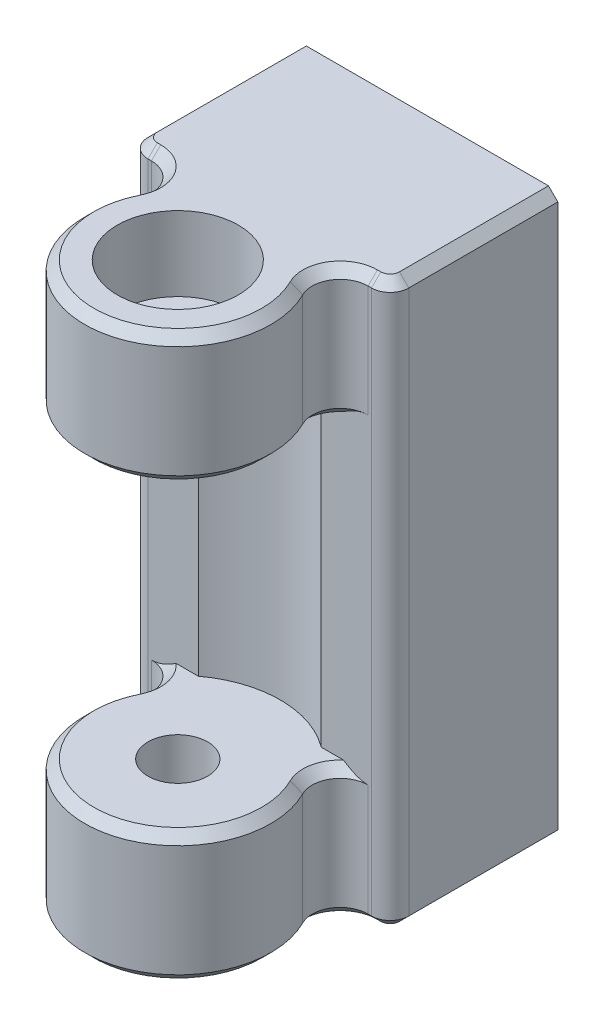
SolidWorks part; units mm, degrees
material "ABS"
ref_plane "Alzado" through (0, 0, 0) normal (0, 0, 1) x (1, 0, 0)
ref_plane "Planta" through (0, 0, 0) normal (0, 1, 0) x (1, 0, 0)
ref_plane "Vista lateral" through (0, 0, 0) normal (1, 0, 0) x (0, 0, -1)
sketch "Croquis2" plane through (0, 0, 0) normal (0, 1, 0) x (0, 0, -1)
  line L0 (0, -7) -> (0, 7)
  line L1 (0, 0) -> (-27.4728, 0) construction
  line L2 (0, 7) -> (-9, 7)
  line L3 (-9, 7) -> (-9, 5.8172)
  line L4 (-9, -7) -> (-9, -5.8172)
  line L5 (0, -7) -> (-9, -7)
  arc A2 (-11.1692, 4.4748) -> (-11.1692, -4.4748) centre (-13.4, 0) ccw
  arc A3 (-9, 5.8172) -> (-11.1692, 4.4748) centre (-10.5, 5.8172) cw
  circle A4 centre (-13.4, 0) radius 1.6
  arc A5 (-9, -5.8172) -> (-11.1692, -4.4748) centre (-10.5, -5.8172) ccw
  dimension "D1" = 14
  dimension "D2" = 9
  dimension "D3" = 10
  dimension "D5" = 1.5
  dimension "D6" = 3.2
  dimension "D4" = 13.4
extrude "Saliente-Extruir1" add sketch "Croquis2" along normal mid plane 30.2
sketch "Croquis6" plane through (0, 0, 0) normal (0, 1, 0) x (1, 0, 0)
  line L0 (-7, -9) -> (-3.3, -9)
  line L1 (3.3, -9) -> (7, -9)
  line L2 (-7, -9) -> (-7, -18.9)
  line L3 (-7, -18.9) -> (7, -18.9)
  line L4 (7, -18.9) -> (7, -9)
  arc A0 (3.3, -9) -> (-3.3, -9) centre (0, -13.4) ccw
  dimension "D1" = 11
extrude "Cortar-Extruir4" cut sketch "Croquis6" against normal mid plane 16.2
sketch "Croquis4" plane through (0, 15.1, 0) normal (0, 1, 0) x (1, 0, 0)
  circle A0 centre (0, -13.4) radius 3.25
  dimension "D1" = 6.5
extrude "Cortar-Extruir2" cut sketch "Croquis4" against normal blind 4 and the other way through all
sketch "Croquis5" plane through (0, -15.1, 0) normal (0, -1, 0) x (1, 0, 0)
  line L0 (7, 0) -> (-7, 0) construction
  line L1 (1.5011, 10.8) -> (3.0022, 13.4)
  line L2 (3.0022, 13.4) -> (1.5011, 16)
  line L3 (1.5011, 16) -> (-1.5011, 16)
  line L4 (-1.5011, 16) -> (-3.0022, 13.4)
  line L5 (-3.0022, 13.4) -> (-1.5011, 10.8)
  line L6 (-1.5011, 10.8) -> (1.5011, 10.8)
  circle A0 centre (0, 13.4) radius 2.6 construction
  dimension "D1" = 5.2
extrude "Cortar-Extruir3" cut sketch "Croquis5" against normal blind 4
fillet "Redondeo2" radius 1 2 edges at (-7, 0, 9) (7, 0, 9)
chamfer "Chaflán1" distance 0.5 angle 45 24 edges at (-4.5417, 8.1, 9.7106) (4.5417, 8.1, 9.7106) (0, 8.1, 18.4) (-4.5417, -8.1, 9.7106) (4.5417, -8.1, 9.7106) (0, -8.1, 18.4) (-7, 15.1, 4) (-6.7071, 15.1, 8.7071) (-5.9086, 15.1, 9) (-4.5417, 15.1, 9.7106) (0, 15.1, 18.4) (4.5417, 15.1, 9.7106) (5.9086, 15.1, 9) (6.7071, 15.1, 8.7071) (7, 15.1, 4) (-7, -15.1, 4) (-6.7071, -15.1, 8.7071) (-5.9086, -15.1, 9) (-4.5417, -15.1, 9.7106) (0, -15.1, 18.4) (4.5417, -15.1, 9.7106) (5.9086, -15.1, 9) (6.7071, -15.1, 8.7071) (7, -15.1, 4)
